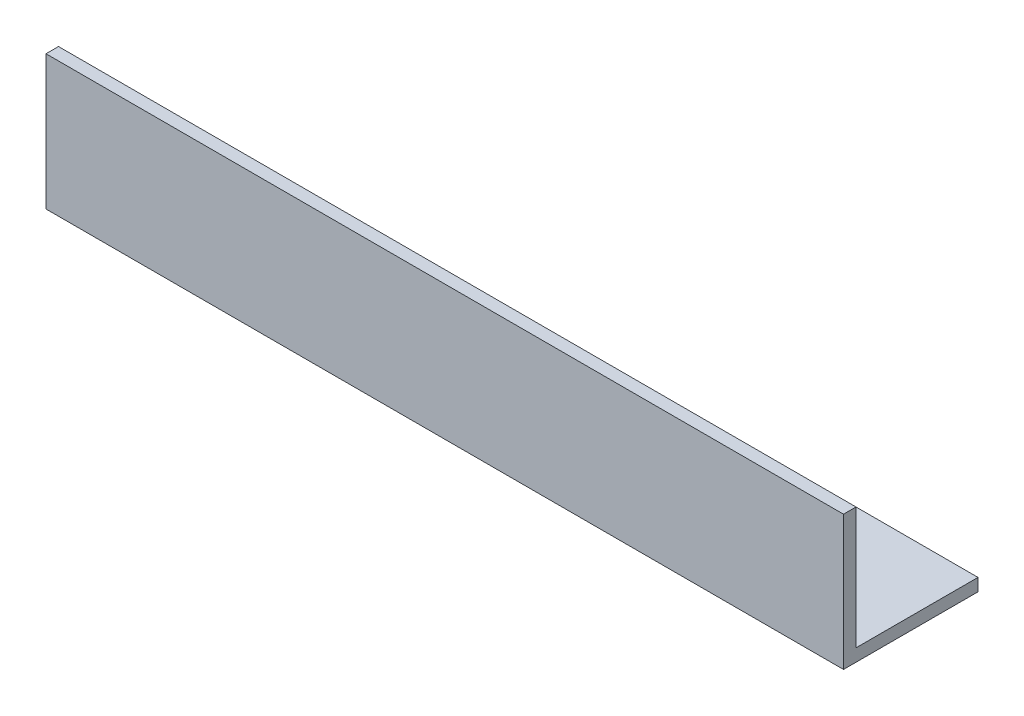
SolidWorks part; units mm, degrees
ref_plane "Спереди" through (0, 0, 0) normal (0, 0, 1) x (1, 0, 0)
ref_plane "Сверху" through (0, 0, 0) normal (0, 1, 0) x (1, 0, 0)
ref_plane "Справа" through (0, 0, 0) normal (1, 0, 0) x (0, 0, -1)
sketch "Эскиз1" plane through (0, 0, 0) normal (1, 0, 0) x (0, 0, -1)
  line L0 (0, 43) -> (0, 0)
  line L1 (0, 0) -> (43, 0)
extrude "Вытянуть-Тонкостенный1" add sketch "Эскиз1" along normal blind 255 thin thin type one direction reverse wall 4
sketch "Эскиз2" plane through (0, 0, 0) normal (0, -1, 0) x (1, 0, 0)
  circle A0 centre (80, -23) radius 5
  circle A1 centre (180, -23) radius 5
  dimension "D1" = 2
extrude "Вырез-Вытянуть1" cut sketch "Эскиз2" against normal through all
